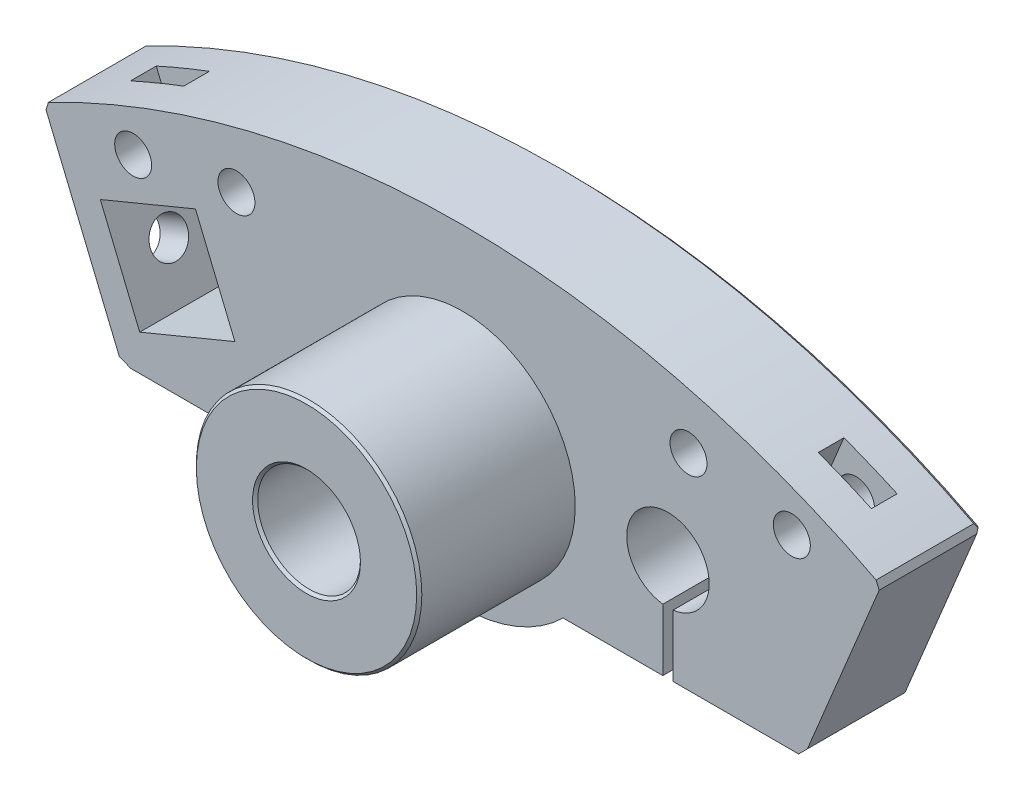
SolidWorks part; units mm, degrees
ref_plane "Front Plane" through (0, 0, 0) normal (0, 0, 1) x (1, 0, 0)
ref_plane "Top Plane" through (0, 0, 0) normal (0, 1, 0) x (1, 0, 0)
ref_plane "Right Plane" through (0, 0, 0) normal (1, 0, 0) x (0, 0, -1)
sketch "Sketch1" plane through (0, 0, 0) normal (0, 0, 1) x (1, 0, 0)
  line L0 (-46.9014, 0) -> (43.5211, 0) construction
  line L1 (0, 38.5211) -> (0, -80.4339) construction
  line L2 (-33.5349, -69.25) -> (36.7559, -69.25) construction
  line L3 (0, -69.25) -> (-37.9703, 22.4183) construction
  line L4 (-40.7467, 8.1836) -> (-33.2148, -10)
  line L5 (-25.9885, 6.5901) -> (-35.2504, 2.7537)
  line L6 (-35.2504, 2.7537) -> (-31.414, -6.5082)
  line L7 (-31.414, -6.5082) -> (-22.1521, -2.6718)
  line L8 (-22.1521, -2.6718) -> (-25.9885, 6.5901)
  line L9 (-33.2148, -10) -> (-9.798, -10)
  line L10 (33.2148, -10) -> (20.5, -10)
  line L11 (40.7467, 8.1836) -> (33.2148, -10)
  line L12 (20, 7.6703) -> (20, -11.9024) construction
  line L13 (19.5, -3.9812) -> (19.5, -10)
  line L14 (20.5, -3.9812) -> (20.5, -10)
  line L15 (19.5, -10) -> (9.798, -10)
  arc A0 (20.5, -3.9812) -> (19.5, -3.9812) centre (20, 0) ccw
  circle A1 centre (-28.7013, 0.041) radius 5.0125 construction
  arc A2 (40.7467, 8.1836) -> (-40.7467, 8.1836) centre (0, -69.25) ccw
  arc A5 (-9.798, -10) -> (9.798, -10) centre (0, 0) ccw
  circle A6 centre (0, 0) radius 5
  circle A7 centre (-32.0522, 8.1309) radius 1.8
  circle A8 centre (32.0522, 8.1309) radius 1.8
  circle A9 centre (-22, 10) radius 1.8
  circle A10 centre (22, 10) radius 1.8
  dimension "D1" = 20
  dimension "D2" = 8.025
  dimension "D7" = 75
  dimension "D8" = 175
  dimension "D9" = 3
  dimension "D10" = 14
  dimension "D12" = 10
  dimension "D13" = 3.6
  dimension "D15" = 3.6
  dimension "D16" = 22
  dimension "D17" = 79.25
  dimension "D3" = 69.25
  dimension "D4" = 22.5
  dimension "D5" = 10.025
  dimension "D6" = 90
  dimension "D11" = 10
  dimension "D14" = 0.5
extrude "Boss-Extrude1" add sketch "Sketch1" along normal blind 10
chamfer "Chamfer1" distance 0.5 5 edges at (-33.3322, -1.8772, 0) (-26.7831, -4.59, 0) (-24.0703, 1.9592, 0) (-30.6195, 4.6719, 0) (20, 4.0125, 0)
ref_plane "Plane1" through (0, 0, 3.75) normal (0, 0, 1) x (1, 0, 0)
sketch "Sketch3" plane through (0, 0, 3.75) normal (0, 0, 1) x (1, 0, 0)
  line L0 (-56.5816, 0) -> (49.5436, 0) construction
  line L1 (0, 34.2126) -> (0, -24.5915) construction
  line L2 (-26.7831, -4.59) -> (-35.1783, 15.678) construction
  line L3 (-31.414, -6.5082) -> (-22.1521, -2.6718) construction
  line L4 (-37.0768, 12.9445) -> (-33.5676, 4.4725)
  line L5 (-33.5676, 4.4725) -> (-28.3938, 6.6155)
  line L6 (-31.903, 15.0875) -> (-28.3938, 6.6155)
  line L7 (-37.0768, 12.9445) -> (-31.903, 15.0875)
  line L8 (37.0768, 12.9445) -> (33.5676, 4.4725)
  line L9 (33.5676, 4.4725) -> (28.3938, 6.6155)
  line L10 (31.903, 15.0875) -> (28.3938, 6.6155)
  line L11 (37.0768, 12.9445) -> (31.903, 15.0875)
  circle A0 centre (-32.0522, 8.1309) radius 1.8 construction
  point P15 (-30.9807, 5.544)
  dimension "D1" = 22.5
  dimension "D3" = 2.8
  dimension "D4" = 2.8
extrude "Cut-Extrude2" cut sketch "Sketch3" along normal blind 2.5
chamfer "Chamfer2" distance 0.5 angle 45 7 edges at (14.649, -10, 0) (0, -14, 0) (-21.5064, -10, 0) (-36.9808, -0.9082, 0) (26.8574, -10, 0) (36.9808, -0.9082, 0) (0, 18.25, 0)
sketch "Sketch4" plane through (-29.1145, -12.0596, 0) normal (0.9239, 0.3827, 0) x (0, 0, -1)
  line L0 (-11.0407, 11.0213) -> (-0.5, 11.0213) construction
  line L1 (-0.5, 6.0088) -> (-0.5, 16.0338) construction
  line L2 (-5.25, 6.0088) -> (-5.25, 12.0172) construction
  line L3 (-10, 6.0088) -> (-0.5, 6.0088) construction
  circle A0 centre (-5.25, 11.0213) radius 1.8
  dimension "D1" = 3.6
extrude "Cut-Extrude3" cut sketch "Sketch4" against normal blind 10
chamfer "Chamfer3" distance 0.5 angle 45 4 edges at (40.7467, 8.1836, 5.25) (33.2148, -10, 5.25) (-33.2148, -10, 5.25) (-40.7467, 8.1836, 5.25) first distance on face at (36.9808, -0.9082, 5.25) first distance on face at (26.8574, -10, 5.25) first distance on face at (-36.7927, -1.3623, 5.25) first distance on face at (0, 13.2168, 5.25)
sketch "Sketch7" plane through (0, 0, 10) normal (0, 0, 1) x (1, 0, 0)
  circle A0 centre (0, 0) radius 10.975
  circle A1 centre (0, 0) radius 5
  dimension "D1" = 21.95
  dimension "D2" = 10
extrude "Boss-Extrude2" add sketch "Sketch7" along normal blind 15.18
sketch "Sketch8" plane through (0, 0, 0) normal (0, 0, 1) x (1, 0, 0)
  circle A0 centre (0, 0) radius 8.5125
  dimension "D1" = 17.025
extrude "Cut-Extrude6" cut sketch "Sketch8" along normal blind 11.18
sketch "Sketch9" plane through (0, 0, 0) normal (0, 0, 1) x (1, 0, 0)
  circle A0 centre (0, 0) radius 9.5125
  dimension "D1" = 19.025
extrude "Cut-Extrude8" cut sketch "Sketch9" along normal blind 6.32
chamfer "Chamfer4" distance 0.25 angle 45 3 edges at (5, 0, 25.18) (10.975, 0, 25.18) (8.5125, 0, 6.32)
